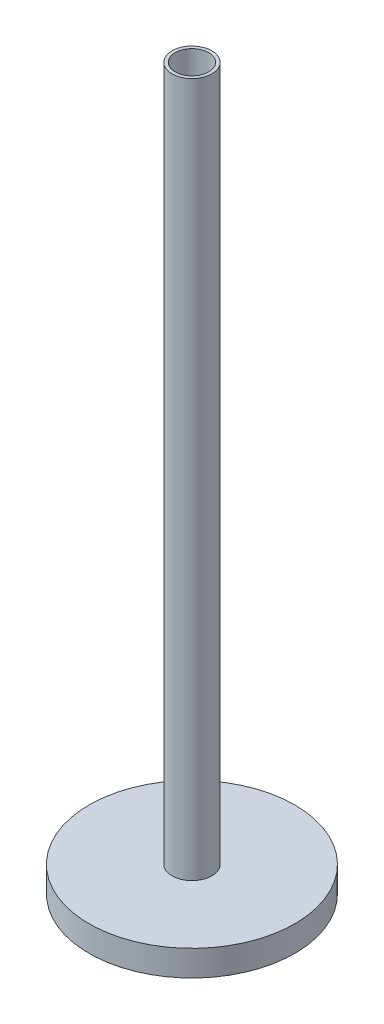
SolidWorks part; units mm, degrees
ref_plane "Front Plane" through (0, 0, 0) normal (0, 0, 1) x (1, 0, 0)
ref_plane "Top Plane" through (0, 0, 0) normal (0, 1, 0) x (1, 0, 0)
ref_plane "Right Plane" through (0, 0, 0) normal (1, 0, 0) x (0, 0, -1)
sketch "Sketch1" plane through (0, 0, 0) normal (0, 1, 0) x (1, 0, 0)
  circle A0 centre (0, 0) radius 7.75
  circle A1 centre (0, 0) radius 6.5
  dimension "D1" = 15.5
  dimension "D2" = 13
extrude "Boss-Extrude1" add sketch "Sketch1" along normal blind 270
sketch "Sketch2" plane through (0, 0, 0) normal (0, -1, 0) x (-1, 0, 0)
  circle A0 centre (0, 0) radius 40.0005
  circle A1 centre (0, 0) radius 7.75
  dimension "D1" = 15.5
extrude "Boss-Extrude2" add sketch "Sketch2" along normal blind 10
extrude "Boss-Extrude3" add sketch "Sketch1<2>" against normal blind 20.4764
sketch "Sketch1<2>" plane through (0, 0, 0) normal (0, 1, 0) x (1, 0, 0) same geometry as "Sketch1"
